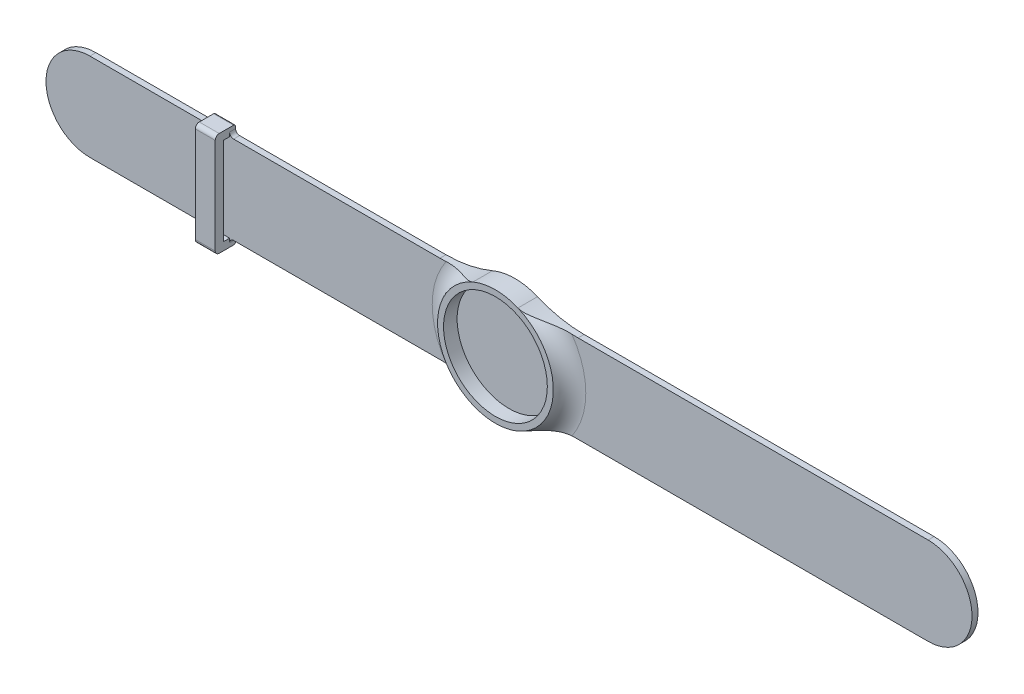
SolidWorks part; units mm, degrees
ref_plane "Спереди" through (0, 0, 0) normal (0, 0, 1) x (1, 0, 0)
ref_plane "Сверху" through (0, 0, 0) normal (0, 1, 0) x (1, 0, 0)
ref_plane "Справа" through (0, 0, 0) normal (1, 0, 0) x (0, 0, -1)
other "Configuration Table"
sketch "Эскиз3" plane through (0, 0, 0) normal (0, 0, 1) x (1, 0, 0)
  line L0 (-9.4472, 11) -> (9.4472, 11) construction
  line L1 (-105, 11) -> (-17.2988, 11)
  line L2 (-105, 11) -> (-105, -11)
  line L3 (-105, -11) -> (-17.2988, -11)
  line L4 (105, 11) -> (105, -11)
  line L5 (-105, 11) -> (105, -11) construction
  line L6 (-105, -11) -> (105, 11) construction
  line L7 (17.2988, 11) -> (105, 11)
  line L8 (-9.4472, -11) -> (9.4472, -11) construction
  line L9 (17.2988, -11) -> (105, -11)
  line L10 (-75, 11) -> (-75, -11) construction
  arc A0 (5.6367, 13.3596) -> (-5.6367, 13.3596) centre (0, 0) ccw
  circle A1 centre (-105, 0) radius 11
  circle A2 centre (105, 0) radius 11
  arc A3 (-14.4038, 1.6678) -> (-14.4038, -1.6678) centre (0, 0) ccw construction
  arc A4 (-5.6367, 13.3596) -> (-17.2988, 11) centre (-17.2988, 41) cw
  arc A5 (5.6367, 13.3596) -> (17.2988, 11) centre (17.2988, 41) ccw
  arc A6 (-5.6367, -13.3596) -> (5.6367, -13.3596) centre (0, 0) ccw
  arc A7 (-14.4038, -1.6678) -> (-9.4472, -11) centre (0, 0) ccw construction
  arc A8 (-5.6367, -13.3596) -> (-17.2988, -11) centre (-17.2988, -41) ccw
  arc A9 (5.6367, -13.3596) -> (17.2988, -11) centre (17.2988, -41) cw
  point P11 (9.4472, 11)
  point P32 (-75, 11)
  point P33 (-75, -11)
  dimension "D1" = 29
  dimension "D4" = 30
  dimension "D5" = 30
  dimension "D6" = 30
  dimension "D7" = 30
  dimension "D2" = 105
  dimension "D3" = 22
  dimension "D8" = 30
extrude "Бобышка-Вытянуть2" add sketch "Эскиз3" along normal blind 1.5 contours L2 A1 | L2 A1 | A1 L3 A0 L1 | L1 A0 L3 | A2 L1 A0 L3 | L4 A2 | L4 A2 | A0 A4 L1 L2 L3 A8 A6 A9 L9 L4 L7 A5 region at (-100.3315, 0, 0) region at (0, 0, 0) region at (-109.6685, 0, 0) region at (109.6685, 0, 0) region at (100.3315, 0, 0)
sketch "Эскиз5" plane through (0, 0, 1.5) normal (0, 0, 1) x (1, 0, 0)
  circle A0 centre (0, 0) radius 13
  circle A1 centre (0, 0) radius 14.5
  dimension "D1" = 26
extrude "Бобышка-Вытянуть3" add sketch "Эскиз5" along normal blind 3.4
fillet "Скругление4" radius 5 1 edges at (-14.5, 0, 1.5)
fillet "Скругление5" radius 5 1 edges at (14.5, 0, 1.5)
sketch "Эскиз6" plane through (0, 0, 1.5) normal (0, 0, 1) x (1, 0, 0)
  line L0 (-75, 11) -> (-75, -11) construction
  line L1 (-105, 11) -> (-17.2988, 11) construction
  line L2 (-105, -11) -> (-17.2988, -11) construction
  line L4 (-75, 11) -> (-70, 11)
  line L5 (-75, 11) -> (-75, 13)
  line L6 (-75, 13) -> (-70, 13)
  line L7 (-70, 11) -> (-70, 13)
  line L8 (-75, -11) -> (-70, -11)
  line L9 (-75, -11) -> (-75, -13)
  line L10 (-75, -13) -> (-70, -13)
  line L11 (-70, -11) -> (-70, -13)
  point P13 (0, 0)
  dimension "D1" = 30
  dimension "D2" = 5
  dimension "D3" = 2
  dimension "D4" = 5
  dimension "D5" = 2
extrude "Бобышка-Вытянуть8" add sketch "Эскиз6" against normal blind 1.5
extrude "Бобышка-Вытянуть9" add sketch "Эскиз6<2>" along normal blind 3.6
sketch "Эскиз6<2>" plane through (0, 0, 1.5) normal (0, 0, 1) x (1, 0, 0) same geometry as "Эскиз6"
sketch "Эскиз10" plane through (0, 11, 0) normal (0, -1, 0) x (1, 0, 0)
  line L0 (-70, 0) -> (-70, 5.1) construction
  line L1 (-75, 5.1) -> (-70, 5.1)
  line L2 (-75, 5.1) -> (-75, 3.05)
  line L3 (-75, 3.05) -> (-70, 3.05)
  line L4 (-70, 5.1) -> (-70, 3.05)
  dimension "D1" = 2.05
extrude "Бобышка-Вытянуть10" add sketch "Эскиз10" along normal up to next
ref_plane "Плоскость1" through (-75, -13, 0) normal (1, 0, 0) x (0, 0, -1)
fillet "Скругление8" radius 1 1 edges at (-72.5, -13, 5.1)
fillet "Скругление10" radius 0.5 1 edges at (-72.5, -13, 0)
fillet "Скругление11" radius 0.5 1 edges at (-72.5, 13, 0)
fillet "Скругление12" radius 1 1 edges at (-72.5, 13, 5.1)
fillet "Скругление13" radius 1 4 edges at (-75, -11, 0.75) (-70, -11, 0.75) (-70, 11, 0.75) (-75, 11, 0.75)
